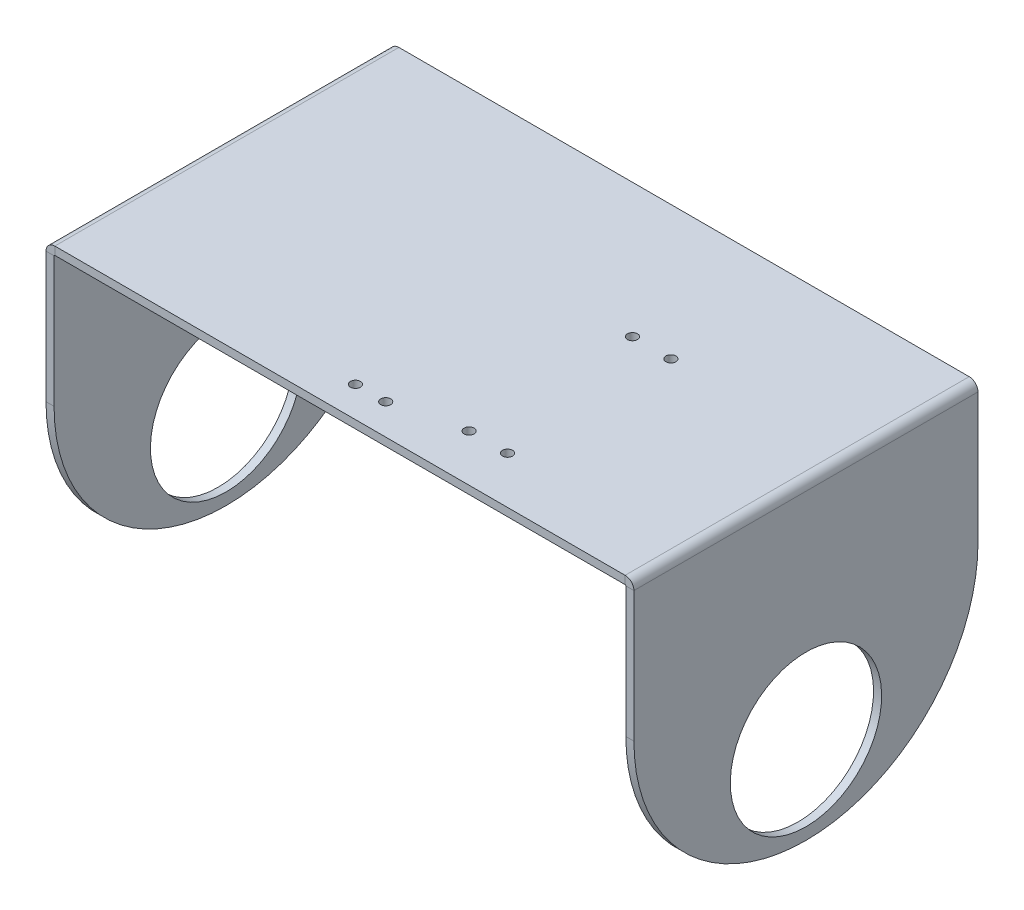
SolidWorks part; units mm, degrees
note: The reader was unsure of these and kept them because the rebuilt part matched: flange length of "Edge-Flange2".
ref_plane "Front Plane" through (0, 0, 0) normal (0, 0, 1) x (1, 0, 0)
ref_plane "Top Plane" through (0, 0, 0) normal (0, 1, 0) x (1, 0, 0)
ref_plane "Right Plane" through (0, 0, 0) normal (1, 0, 0) x (0, 0, -1)
sketch "Sketch2" plane through (0, 0, 0) normal (0, 1, 0) x (1, 0, 0)
  line L0 (0, 0) -> (582.8, 0)
  line L1 (0, 0) -> (0, 341.07)
  line L2 (0, 341.07) -> (582.8, 341.07)
  line L3 (582.8, 341.07) -> (582.8, 0)
  dimension "D1" = 582.8
  dimension "D2" = 341.07
sketch "Sketch17" plane through (0, 0, 0) normal (1, 0, 0) x (0, 0, -1)
  line L0 (341.07, 0) -> (341.07, -91.765)
  line L1 (341.07, 0) -> (0, 0) construction
  line L2 (341.07, -91.765) -> (0, -91.765)
  line L3 (0, -91.765) -> (0, 0)
base flange "Base-Flange5" sketch "Sketch2" thickness 8 reverse thickness direction no parameters "D1"=0.7366
edge flange "Edge-Flange2" sketch "Sketch37" flange profiles "Sketch37", "Sketch38" flange angle 90 flange length 138 flange position material inside bend radius 0.7366 thickness 8 relief rectangular parameters "D6"=10, "D8"=1
sketch "Sketch37" plane through (0, -8, 0) normal (-1, 0, 0) x (0, 0, -1)
  line L2 (0, 0) -> (0, 130)
  line L3 (0, 130) -> (341.07, 130)
  line L4 (341.07, 130) -> (341.07, 0)
  line L7 (341.07, 0) -> (0, 0) construction
  line L8 (341.07, 0) -> (0, 0)
  dimension "D1" = 130
sketch "Sketch38" plane through (582.8, -8, 0) normal (1, 0, 0) x (0, 0, 1)
  line L0 (0, 0) -> (-341.07, 0) construction
  line L1 (0, 0) -> (-341.07, 0)
  line L2 (-341.07, 0) -> (-341.07, 130)
  line L3 (-341.07, 130) -> (0, 130)
  line L4 (0, 130) -> (0, 0)
bend "EdgeBend3" bend radius 0.7366 bend angle 90 parameters "D5"=1
bend "EdgeBend4" bend radius 0.7366 bend angle 90 parameters "D5"=2
ref_plane "Plane1" through (4, 0, 0) normal (-1, 0, 0) x (0, 0, 1)
sketch "Sketch39" plane through (4, 0, 0) normal (-1, 0, 0) x (0, 0, 1)
  line L4 (0, -8.7366) -> (-341.07, -8.7366)
  line L5 (-341.07, -8.7366) -> (-341.07, -138)
  line L6 (-341.07, -138) -> (0, -138)
  line L7 (0, -138) -> (0, -8.7366)
  line L10 (-341.07, -138) -> (0, -138)
  arc A0 (-341.07, -138) -> (0, -138) centre (-170.535, -138) ccw
  dimension "D2" = 170.535
  dimension "D1" = 0
extrude "Boss-Extrude4" add sketch "Sketch39" along normal mid plane 8 contours A0 L10
sketch "Sketch40" plane through (0, 0, 0) normal (-1, 0, 0) x (0, 0, 1)
  circle A0 centre (-170.535, -221.7738) radius 75
  dimension "D1" = 150
sketch "Sketch43" plane through (0, 0, 0) normal (0, 1, 0) x (1, 0, 0)
  line L0 (8.7366, 0) -> (574.0634, 0)
  line L1 (291.4, 0) -> (291.4, 30.31)
  line L2 (291.4, 30.31) -> (306.4, 30.31)
  line L3 (291.4, 30.31) -> (276.4, 30.31)
  dimension "D1" = 30.31
  dimension "D2" = 15
  dimension "D3" = 15
hole_wizard "Ø10.0mm Dowel Hole1" positions "3DSketch1" profile "Sketch44" hole size "Ø10.0" standard "ISO" end condition through all
sketch3d "3DSketch1"
  point P0 (306.4, 0, -30.31)
  point P3 (276.4, 0, -30.31)
sketch "Sketch44" plane through (306.4, 0, -30.31) normal (1, 0, 0) x (0, 0, 1)
  line L0 (0, 0) -> (0, 308.535)
  line L1 (0, 308.535) -> (5, 308.535)
  line L2 (5, 308.535) -> (5, 0)
  line L5 (5, 0) -> (0, 0)
  line L11 (0, -6.35) -> (0, 107.95) construction
  dimension "Thru Hole Dia." = 10
  dimension "Thru Hole Depth" = 308.535
ref_plane "Plane7" through (578.8, 0, 0) normal (1, 0, 0) x (0, 0, -1)
sketch "Sketch46" plane through (578.8, 0, 0) normal (1, 0, 0) x (0, 0, -1)
  line L0 (0, -138) -> (341.07, -138)
  arc A0 (0, -138) -> (341.07, -138) centre (170.535, -138) ccw
extrude "Boss-Extrude5" add sketch "Sketch46" along normal mid plane 8
extrude "Cut-Extrude2" cut sketch "Sketch40" against normal through all both and the other way through all contours A0 normal cut yes
sketch "Sketch49" plane through (0, 0, 0) normal (0, 1, 0) x (1, 0, 0)
  line L0 (372.86, 46.56) -> (410.94, 46.56)
  line L1 (8.7366, 0) -> (574.0634, 0) construction
  circle A1 centre (306.4, 30.31) radius 5 construction
  dimension "D2" = 66.46
  dimension "D1" = 46.56
  dimension "D3" = 38.08
hole_wizard "Ø10.0mm Dowel Hole2" positions "3DSketch2" profile "Sketch50" hole size "Ø10.0" standard "ISO" end condition through all
sketch3d "3DSketch2"
  point P0 (372.86, 0, -46.56)
  point P3 (410.94, 0, -46.56)
sketch "Sketch50" plane through (372.86, 0, -46.56) normal (1, 0, 0) x (0, 0, 1)
  line L0 (0, 0) -> (0, 308.535)
  line L1 (0, 308.535) -> (5, 308.535)
  line L2 (5, 308.535) -> (5, 0)
  line L5 (5, 0) -> (0, 0)
  line L11 (0, -6.35) -> (0, 107.95) construction
  dimension "Thru Hole Dia." = 10
  dimension "Thru Hole Depth" = 308.535
sketch "Sketch51" plane through (0, 0, 0) normal (0, 1, 0) x (1, 0, 0)
  line L0 (372.86, 46.56) -> (372.86, 208.49)
  line L1 (410.94, 46.56) -> (410.94, 208.49)
  dimension "D1" = 161.93
  dimension "D2" = 161.93
hole_wizard "Ø10.0mm Dowel Hole3" positions "3DSketch3" profile "Sketch52" hole size "Ø10.0" standard "ISO" end condition through all
sketch3d "3DSketch3"
  point P0 (410.94, 0, -208.49)
  point P3 (372.86, 0, -208.49)
sketch "Sketch52" plane through (410.94, 0, -208.49) normal (1, 0, 0) x (0, 0, 1)
  line L0 (0, 0) -> (0, 308.535)
  line L1 (0, 308.535) -> (5, 308.535)
  line L2 (5, 308.535) -> (5, 0)
  line L5 (5, 0) -> (0, 0)
  line L11 (0, -6.35) -> (0, 107.95) construction
  dimension "Thru Hole Dia." = 10
  dimension "Thru Hole Depth" = 308.535
sketch "Bend-Lines8" [suppressed] plane through (0, 0, 0) normal (0, 1, 0) x (1, 0, 0)
sketch "Bounding-Box8" [suppressed] plane through (0, 0, 0) normal (0, 1, 0) x (1, 0, 0)
sheet metal parameters "Sheet-Metal7" thickness 8 parameters "D1"=0.7366
flat pattern "Flat-Pattern7" [suppressed]
sketch "Bend-Lines9" plane through (0, 0, 0) normal (0, 1, 0) x (1, 0, 0)
sketch3d "Bounding-Box9" [suppressed]
  line L0 (-582.8, 341.07, 0) -> (0, 341.07, 0) construction
  line L1 (-582.8, 0, 0) -> (0, 0, 0) construction
  line L2 (-582.8, 341.07, 0) -> (-582.8, 0, 0) construction
  line L3 (0, 341.07, 0) -> (0, 0, 0) construction
sheet metal parameters "Sheet-Metal8" thickness 8 parameters "D1"=0.7366
flat pattern "Flat-Pattern7"
sketch "Bend-Lines9" plane through (0, 0, 0) normal (0, 1, 0) x (1, 0, 0)
  line L0 (577.7835, 0) -> (577.7835, 341.07) construction
  line L1 (5.0165, 341.07) -> (5.0165, 0) construction
  line L2 (577.7835, 0) -> (577.7835, 341.07) construction
  line L3 (5.0165, 341.07) -> (5.0165, 0) construction
sketch3d "Bounding-Box9" [suppressed]
  line L0 (710.767, 341.07, 0) -> (-127.967, 341.07, 0) construction
  line L1 (710.767, 0, 0) -> (-127.967, 0, 0) construction
  line L2 (710.767, 341.07, 0) -> (710.767, 0, 0) construction
  line L3 (-127.967, 341.07, 0) -> (-127.967, 0, 0) construction
bend of the flat pattern "Flatten-<EdgeBend3>1"
bend of the flat pattern "Flatten-<EdgeBend4>1"
sheet metal parameters "Sheet-Metal10" thickness 8 parameters "D1"=0.7366
flat pattern "Flat-Pattern7"
sketch "Bend-Lines9" plane through (0, 0, 0) normal (0, 1, 0) x (1, 0, 0)
  line L0 (577.7835, 0) -> (577.7835, 341.07) construction
  line L1 (5.0165, 341.07) -> (5.0165, 0) construction
  line L2 (577.7835, 0) -> (577.7835, 341.07) construction
  line L3 (5.0165, 341.07) -> (5.0165, 0) construction
sketch3d "Bounding-Box9" [suppressed]
  line L0 (-298.502, 341.07, 0) -> (710.767, 341.07, 0) construction
  line L1 (-298.502, 0, 0) -> (710.767, 0, 0) construction
  line L2 (-298.502, 341.07, 0) -> (-298.502, 0, 0) construction
  line L3 (710.767, 341.07, 0) -> (710.767, 0, 0) construction
bend of the flat pattern "Flatten-<EdgeBend3>1"
bend of the flat pattern "Flatten-<EdgeBend4>1"
sheet metal parameters "Sheet-Metal12" thickness 8 parameters "D1"=0.7366
flat pattern "Flat-Pattern7"
sketch "Bend-Lines9" plane through (0, 0, 0) normal (0, 1, 0) x (1, 0, 0)
  line L0 (577.7835, 0) -> (577.7835, 341.07) construction
  line L1 (5.0165, 341.07) -> (5.0165, 0) construction
  line L2 (577.7835, 0) -> (577.7835, 341.07) construction
  line L3 (5.0165, 341.07) -> (5.0165, 0) construction
sketch3d "Bounding-Box9" [suppressed]
  line L0 (-298.502, 341.07, 0) -> (710.767, 341.07, 0) construction
  line L1 (-298.502, 0, 0) -> (710.767, 0, 0) construction
  line L2 (-298.502, 341.07, 0) -> (-298.502, 0, 0) construction
  line L3 (710.767, 341.07, 0) -> (710.767, 0, 0) construction
bend of the flat pattern "Flatten-<EdgeBend3>1"
bend of the flat pattern "Flatten-<EdgeBend4>1"
sheet metal parameters "Sheet-Metal13" thickness 8 parameters "D1"=0.7366
flat pattern "Flat-Pattern7" [suppressed]
sketch "Bend-Lines9" plane through (0, 0, 0) normal (0, 1, 0) x (1, 0, 0)
  line L0 (577.7835, 0) -> (577.7835, 341.07) construction
  line L1 (5.0165, 341.07) -> (5.0165, 0) construction
  line L2 (577.7835, 0) -> (577.7835, 341.07) construction
  line L3 (5.0165, 341.07) -> (5.0165, 0) construction
sketch3d "Bounding-Box9" [suppressed]
  line L0 (881.302, 341.07, 0) -> (-298.502, 341.07, 0) construction
  line L1 (881.302, 0, 0) -> (-298.502, 0, 0) construction
  line L2 (881.302, 341.07, 0) -> (881.302, 0, 0) construction
  line L3 (-298.502, 341.07, 0) -> (-298.502, 0, 0) construction
bend of the flat pattern "Flatten-<EdgeBend3>1"
bend of the flat pattern "Flatten-<EdgeBend4>1"
sketch "Sketch40-1" [suppressed] plane through (10.033, 0, 0) normal (0, 1, 0) x (0, 0, 1)
  circle A0 centre (-170.535, -221.7738) radius 45
  dimension "D1" = 90
sheet metal parameters "Sheet-Metal14" thickness 8 parameters "D1"=0.7366
flat pattern "Flat-Pattern7" [suppressed]
sketch "Bend-Lines9" plane through (0, 0, 0) normal (0, 1, 0) x (1, 0, 0)
  line L0 (577.7835, 0) -> (577.7835, 341.07) construction
  line L1 (5.0165, 341.07) -> (5.0165, 0) construction
  line L2 (577.7835, 0) -> (577.7835, 341.07) construction
  line L3 (5.0165, 341.07) -> (5.0165, 0) construction
sketch3d "Bounding-Box9" [suppressed]
  line L0 (881.302, 341.07, 0) -> (-298.502, 341.07, 0) construction
  line L1 (881.302, 0, 0) -> (-298.502, 0, 0) construction
  line L2 (881.302, 341.07, 0) -> (881.302, 0, 0) construction
  line L3 (-298.502, 341.07, 0) -> (-298.502, 0, 0) construction
bend of the flat pattern "Flatten-<EdgeBend3>1"
bend of the flat pattern "Flatten-<EdgeBend4>1"
sketch "Sketch40-1" [suppressed] plane through (10.033, 0, 0) normal (0, 1, 0) x (0, 0, 1)
  circle A0 centre (-170.535, -221.7738) radius 45
  dimension "D1" = 90
sheet metal parameters "Sheet-Metal15" thickness 8 parameters "D1"=0.7366
flat pattern "Flat-Pattern7" [suppressed]
sketch "Bend-Lines9" plane through (0, 0, 0) normal (0, 1, 0) x (1, 0, 0)
  line L0 (577.7835, 0) -> (577.7835, 341.07) construction
  line L1 (5.0165, 341.07) -> (5.0165, 0) construction
  line L2 (577.7835, 0) -> (577.7835, 341.07) construction
  line L3 (5.0165, 341.07) -> (5.0165, 0) construction
sketch3d "Bounding-Box9" [suppressed]
  line L0 (881.302, 341.07, 0) -> (-298.502, 341.07, 0) construction
  line L1 (881.302, 0, 0) -> (-298.502, 0, 0) construction
  line L2 (881.302, 341.07, 0) -> (881.302, 0, 0) construction
  line L3 (-298.502, 341.07, 0) -> (-298.502, 0, 0) construction
bend of the flat pattern "Flatten-<EdgeBend3>1"
bend of the flat pattern "Flatten-<EdgeBend4>1"
sketch "Sketch40-1" plane through (10.033, 0, 0) normal (0, 1, 0) x (0, 0, 1)
  circle A0 centre (-170.535, -221.7738) radius 45
  dimension "D1" = 90
sheet metal parameters "Sheet-Metal16" thickness 8 parameters "D1"=0.7366
flat pattern "Flat-Pattern7" [suppressed]
sketch "Bend-Lines9" plane through (0, 0, 0) normal (0, 1, 0) x (1, 0, 0)
  line L0 (577.7835, 0) -> (577.7835, 341.07) construction
  line L1 (5.0165, 341.07) -> (5.0165, 0) construction
  line L2 (577.7835, 0) -> (577.7835, 341.07) construction
  line L3 (5.0165, 341.07) -> (5.0165, 0) construction
sketch3d "Bounding-Box9" [suppressed]
  line L0 (881.302, 341.07, 0) -> (-298.502, 341.07, 0) construction
  line L1 (881.302, 0, 0) -> (-298.502, 0, 0) construction
  line L2 (881.302, 341.07, 0) -> (881.302, 0, 0) construction
  line L3 (-298.502, 341.07, 0) -> (-298.502, 0, 0) construction
bend of the flat pattern "Flatten-<EdgeBend3>1"
bend of the flat pattern "Flatten-<EdgeBend4>1"
sketch "Sketch40-1" plane through (10.033, 0, 0) normal (0, 1, 0) x (0, 0, 1)
  circle A0 centre (-170.535, -221.7738) radius 75
  dimension "D1" = 150
